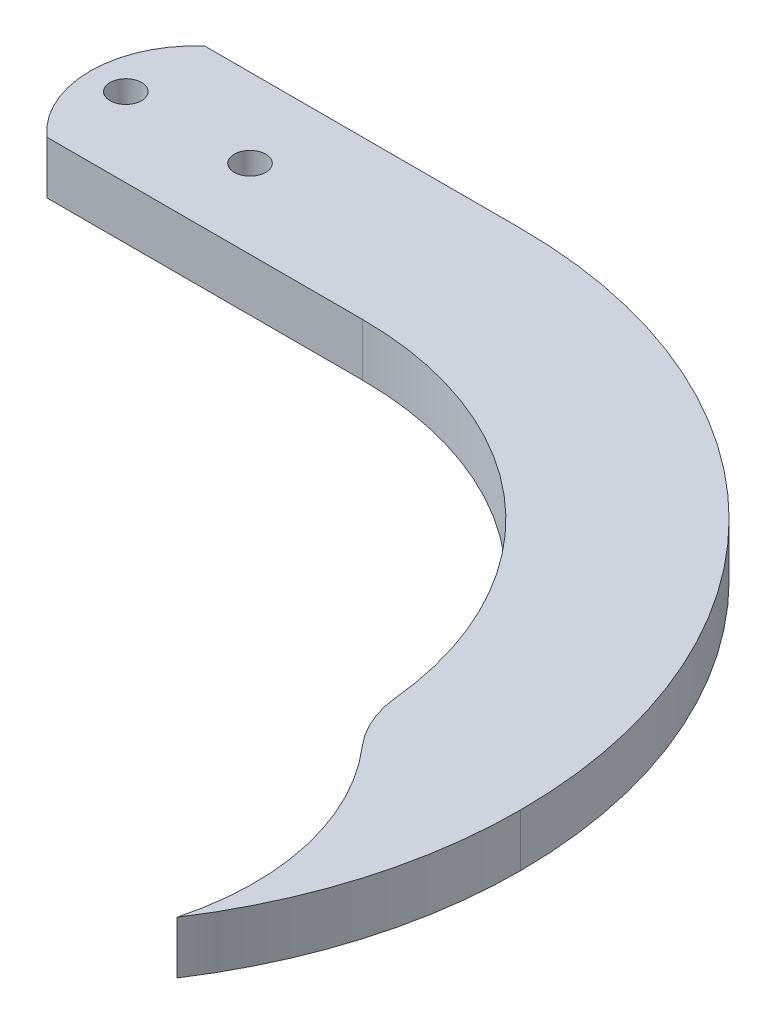
SolidWorks part; units mm, degrees
ref_plane "Front" through (0, 0, 0) normal (0, 0, 1) x (1, 0, 0)
ref_plane "Top" through (0, 0, 0) normal (0, 1, 0) x (1, 0, 0)
ref_plane "Right" through (0, 0, 0) normal (1, 0, 0) x (0, 0, -1)
sketch "Sketch1" plane through (0, 0, 0) normal (0, 1, 0) x (1, 0, 0)
  line L0 (0, 0) -> (30, 0) construction
  line L1 (0, 7.5) -> (30, 7.5)
  line L2 (0, -7.5) -> (30, -7.5)
  line L3 (62.875, -40.375) -> (77.875, -40.375) construction
  arc A0 (0, 7.5) -> (0, -7.5) centre (0, 0) ccw
  arc A5 (30, -7.5) -> (30, 7.5) centre (30, 0) ccw
  arc A6 (30, 0) -> (70.375, -40.375) centre (30, -40.375) cw construction
  arc A7 (77.875, -40.375) -> (30, 7.5) centre (30, -40.375) ccw
  arc A8 (62.875, -40.375) -> (30, -7.5) centre (30, -40.375) ccw
  arc A9 (62.875, -40.375) -> (77.875, -40.375) centre (70.375, -40.375) ccw
  arc A10 (30, 7.5) -> (30, -7.5) centre (30, 0) ccw
  circle A11 centre (0, 0) radius 1.5
  circle A12 centre (11.8, 0) radius 1.5
  point P2 (15, 0)
  point P12 (58.5494, -11.8256)
  dimension "D1" = 30
  dimension "D2" = 7.5
  dimension "D3" = 32.875
  dimension "D4" = 11.8
  dimension "D5" = 3
extrude "Boss-Extrude1" add sketch "Sketch1" along normal blind 5 contours A10 L1 A0 L2 A12 A11 | A5 A10 | A8 A9 A7 A5 region at (9.2136, 0, 0) region at (59.4535, 0, 18.4215) region at (30, 0, 0)
sketch "Sketch2" plane through (0, 5, 0) normal (0, 1, 0) x (1, 0, 0)
  arc A0 (0, 7.5) -> (0, -7.5) centre (0, 0) ccw construction
  arc A1 (0, 7.5) -> (0, -7.5) centre (0, 0) ccw
  arc A2 (0, 7.5) -> (0, -7.5) centre (6.6144, 0) ccw
  point P3 (-0.3109, -7.4936)
  point P5 (-3.3856, 0)
  point P6 (-0.312, 7.4935)
  dimension "D1" = 10
extrude "Cut-Extrude1" cut sketch "Sketch2" against normal blind 10 contours A1 A2
sketch "Sketch3" plane through (0, 5, 0) normal (0, 1, 0) x (1, 0, 0)
  arc A0 (62.875, -40.375) -> (77.875, -40.375) centre (70.375, -40.375) ccw construction
  arc A1 (68.4826, -47.6323) -> (77.875, -40.375) centre (70.375, -40.375) ccw
  arc A2 (77.875, -40.375) -> (70.375, -65.5194) centre (31.9756, -40.375) cw
  arc A3 (62.875, -40.375) -> (70.375, -65.5194) centre (46.2319, -59.03) cw
  arc M7 (62.875, -40.375) -> (77.875, -40.375) centre (70.375, -40.375) ccw
  dimension "D1" = 25
extrude "Boss-Extrude2" add sketch "Sketch3" against normal up to surface (5 mm away) contours A3 A2 M7 region at (73.3834, 5, 52.5441) up to face at (0, 0, 1.5)
sketch "Sketch4" plane through (0, 5, 0) normal (0, 1, 0) x (1, 0, 0)
  arc A0 (68.4826, -47.6323) -> (77.875, -40.375) centre (70.375, -40.375) ccw construction
  arc A1 (70.375, -65.5194) -> (77.875, -40.375) centre (31.9756, -40.375) ccw construction
  arc A2 (70.375, -65.5194) -> (62.875, -40.375) centre (46.2319, -59.03) ccw construction
  arc A3 (68.4826, -47.6323) -> (77.875, -40.375) centre (70.375, -40.375) ccw
  arc A4 (70.375, -65.5194) -> (77.875, -40.375) centre (31.9756, -40.375) ccw
  arc A5 (70.375, -65.5194) -> (62.875, -40.375) centre (46.2319, -59.03) ccw
  arc A6 (62.875, -40.375) -> (68.4826, -47.6323) centre (70.375, -40.375) ccw construction
  arc A7 (62.875, -40.375) -> (68.4826, -47.6323) centre (70.375, -40.375) ccw
  arc M7 (62.875, -40.375) -> (68.4826, -47.6323) centre (70.375, -40.375) ccw
extrude "Cut-Extrude2" cut sketch "Sketch4" against normal blind 10 contours A5 M7 region at (65.3117, 5, 44.2873)
fillet "Fillet1" radius 10 1 edges at (62.875, 2.5, 40.375)
